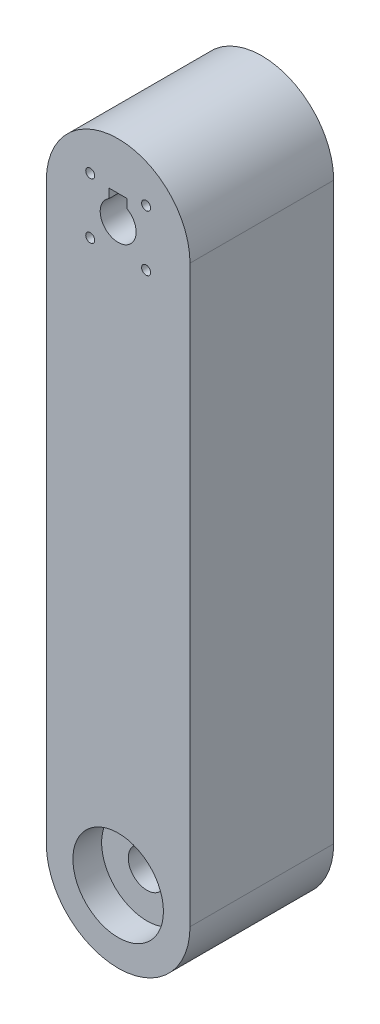
SolidWorks part; units mm, degrees
material "ABS"
ref_plane "Front Plane" through (0, 0, 0) normal (0, 0, 1) x (1, 0, 0)
ref_plane "Top Plane" through (0, 0, 0) normal (0, 1, 0) x (1, 0, 0)
ref_plane "Right Plane" through (0, 0, 0) normal (1, 0, 0) x (0, 0, -1)
sketch "Sketch1" plane through (0, 0, 0) normal (0, 0, 1) x (1, 0, 0)
  line L2 (12.7, 50.8) -> (12.7, -50.8)
  line L4 (-12.7, 50.8) -> (-12.7, -50.8)
  line L5 (12.7, 50.8) -> (-12.7, -50.8) construction
  line L6 (12.7, -50.8) -> (-12.7, 50.8) construction
  arc A0 (-12.7, 50.8) -> (12.7, 50.8) centre (0, 50.8) cw
  arc A1 (-12.7, -50.8) -> (12.7, -50.8) centre (0, -50.8) ccw
  point P0 (0, 0)
  dimension "D1" = 101.6
  dimension "D2" = 25.4
extrude "Boss-Extrude1" add sketch "Sketch1" along normal blind 25.4
sketch "Sketch2" plane through (0, 0, 25.4) normal (0, 0, 1) x (1, 0, 0)
  line L0 (-4.9391, 55.7391) -> (4.9391, 45.8609) construction
  line L1 (4.9391, 55.7391) -> (-4.9391, 45.8609) construction
  line L2 (0, 50.8) -> (0, 59.0413) construction
  circle A0 centre (0, 50.8) radius 3.175
  circle A1 centre (-4.9391, 55.7391) radius 0.7938
  circle A2 centre (-4.9391, 45.8609) radius 0.7937
  circle A3 centre (4.9391, 55.7391) radius 0.7938
  circle A4 centre (4.9391, 45.8609) radius 0.7938
  point P8 (0, 50.8)
  point P9 (0, 50.8)
  dimension "D1" = 6.35
  dimension "D4" = 1.5875
  dimension "D2" = 45
  dimension "D3" = 13.97
extrude "Cut-Extrude1" cut sketch "Sketch2" against normal up to next
sketch "Sketch3" plane through (0, 0, 25.4) normal (0, 0, 1) x (1, 0, 0)
  line L1 (-1.5875, 55.1371) -> (1.5875, 55.1371)
  line L2 (-1.5875, 55.1371) -> (-1.5875, 53.5496)
  line L3 (-1.5875, 53.5496) -> (1.5875, 53.5496)
  line L4 (1.5875, 55.1371) -> (1.5875, 53.5496)
  circle A0 centre (0, 50.8) radius 3.175 construction
  dimension "D1" = 3.175
  dimension "D2" = 1.5875
extrude "Cut-Extrude2" cut sketch "Sketch3" against normal through all
sketch "Sketch4" plane through (0, 0, 25.4) normal (0, 0, 1) x (1, 0, 0)
  circle A0 centre (0, -50.8) radius 8.001
  dimension "D1" = 16.002
extrude "Cut-Extrude3" cut sketch "Sketch4" against normal blind 5.08
ref_plane "Plane1" through (0, 0, 12.7) normal (0, 0, 1) x (1, 0, 0)
mirror "Mirror1" about plane through (0, 0, 12.7) normal (0, 0, 1) of "Cut-Extrude3"
sketch "Sketch5" plane through (0, 0, 20.32) normal (0, 0, 1) x (1, 0, 0)
  circle A0 centre (0, -50.8) radius 3.302
  circle A1 centre (0, -50.8) radius 8.001 construction
  dimension "D1" = 6.604
extrude "Cut-Extrude4" cut sketch "Sketch5" against normal through all
ref_axis "Axis1" through (0, 50.8, 0) along (0, 0, 1)
ref_plane "Plane2" through (0, 0, 12.7) normal (0, 0, 1) x (1, 0, 0)
ref_point "Point1"
ref_plane "Plane3" through (0, 0, -16.31) normal (0, 0, 1) x (1, 0, 0)
ref_axis "Axis2" through (0, -50.8, 78.2601) along (0, 0, 1)
ref_point "Leg frame 2 orgin"
